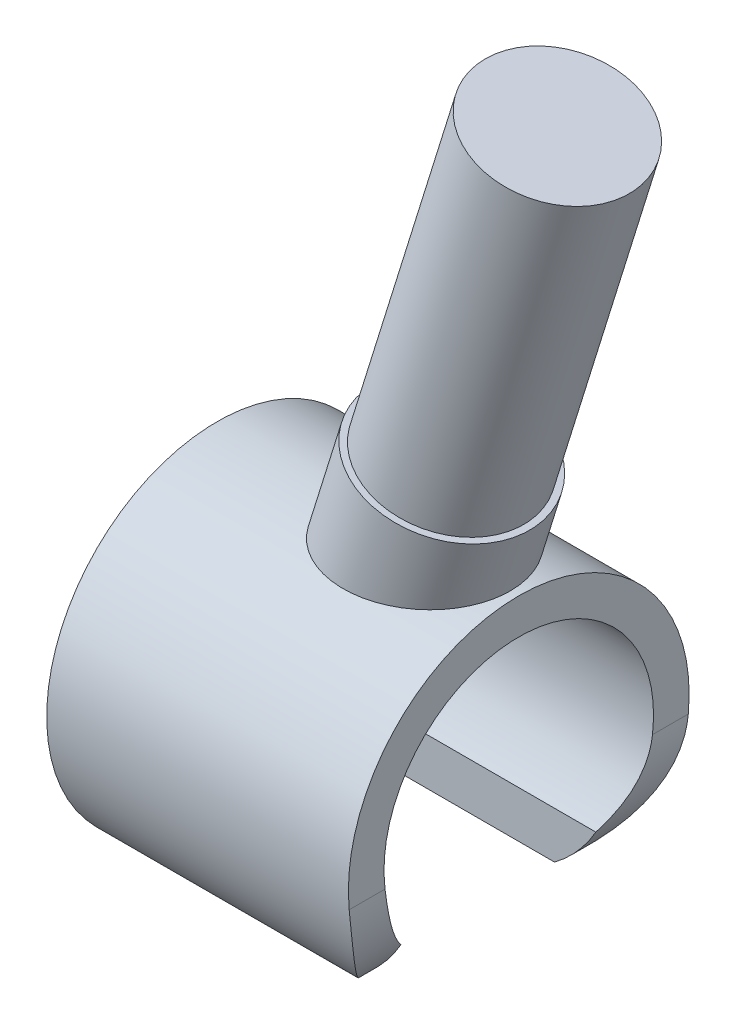
SolidWorks part; units mm, degrees
ref_plane "Ön Düzlem" through (0, 0, 0) normal (0, 0, 1) x (1, 0, 0)
ref_plane "Üst Düzlem" through (0, 0, 0) normal (0, 1, 0) x (1, 0, 0)
ref_plane "Sağ Düzlem" through (0, 0, 0) normal (1, 0, 0) x (0, 0, -1)
sketch "Çizim1" plane through (0, 0, 0) normal (0, 0, 1) x (1, 0, 0)
  line L0 (0, 0) -> (0, -4.88)
  line L1 (0, -4.88) -> (2.12, -4.88)
  line L2 (4.32, -2.68) -> (4.32, 0)
  line L3 (4.32, 0) -> (0, 0)
  line L4 (2.1331, -2.7014) -> (6.6255, 11.7309) construction
  line L5 (0, 0) -> (0, 12.8929) construction
  line L6 (1.7486, 0) -> (2.2429, 1.5877)
  line L7 (4.4771, 0.8923) -> (2.2429, 1.5877)
  line L8 (2.3288, 1.561) -> (2.7254, 2.8352)
  line L9 (2.7254, 2.8352) -> (3.8416, 6.421)
  line L10 (5.904, 5.779) -> (3.8416, 6.421)
  line L11 (4.7878, 2.1932) -> (5.904, 5.779)
  line L12 (4.3912, 0.919) -> (4.7878, 2.1932)
  line L13 (3.9829, -0.6955) -> (4.4771, 0.8923)
  arc A0 (4.32, -2.68) -> (2.12, -4.88) centre (2.12, -2.68) cw
  arc A1 (3.9829, -0.6955) -> (1.7486, 0) centre (3.4681, 1.5872) cw
  point P10 (3.36, 1.24)
  point P17 (4.8728, 6.1)
  point P19 (4.8728, 6.1)
  point P23 (3.36, 1.24)
  dimension "D6" = 2.2
  dimension "D11" = 2.34
  dimension "D1" = 4.32
  dimension "D2" = 17.29
  dimension "D3" = 1.17
  dimension "D4" = 1.24
  dimension "D5" = 3.36
  dimension "D7" = 4.88
  dimension "D8" = 0.09
  dimension "D9" = 1.3345
  dimension "D10" = 6.1
extrude "Yükseklik-Ekstrüzyon1" add sketch "Çizim1" along normal mid plane 4.88 contours L13 A1 L3 L0 L1 A0 L2 | A1 L13 L3 | L3 L13 L7 L6 | L7 L12 L11 L10 L9 L8 region at (1.9971, -2.4847, 0) region at (3.0575, 0.6363, 0) region at (3.133, -0.3188, 0) region at (4.1164, 3.67, 0)
sketch "Çizim2" plane through (0, 0, 0) normal (-1, 0, 0) x (0, 0, 1)
  line L0 (0, 0) -> (0, -4.88) construction
  line L1 (2.44, -4.88) -> (-2.44, -4.88) construction
  line L3 (-1.395, -3.7737) -> (-1.395, -4.4419)
  line L4 (1.395, -3.7737) -> (1.395, -4.4419)
  line L5 (-1.395, -4.4419) -> (-1.395, -4.88)
  line L6 (1.395, -4.4419) -> (1.395, -4.88)
  arc A1 (1.395, -3.7737) -> (-1.395, -3.7737) centre (0, -2.44) ccw
  arc A2 (1.395, -4.4419) -> (-1.395, -4.4419) centre (0, -2.44) ccw
  line M2 (-2.44, -4.88) -> (2.44, -4.88)
  dimension "D1" = 3.86
  dimension "D2" = 4.88
  dimension "D3" = 2.79
  dimension "D4" = 1.1063
extrude "Kes-Ekstrüzyon3" cut sketch "Çizim2" against normal through all contours A1 L0 L6 L4 M2 | L0 A1 L3 L5 M2 region at (0, -2.7343, 0.8154) region at (0, -2.7343, -0.8154)
sketch "Çizim4" plane through (2.1615, 6.944, 0) normal (0.2972, 0.9548, 0) x (0.9548, -0.2972, 0)
  line L0 (1.7596, 0) -> (3.9196, 0) construction
  line L1 (1.7596, -2.44) -> (1.7596, 2.44) construction
  line L2 (3.9196, -2.44) -> (3.9196, 2.44) construction
  line L3 (1.7596, 2.44) -> (3.9196, 2.44)
  line L4 (3.9196, 2.44) -> (3.9196, -2.44)
  line L5 (3.9196, -2.44) -> (1.7596, -2.44)
  line L6 (1.7596, -2.44) -> (1.7596, 2.44)
  circle A0 centre (2.8396, 0) radius 1.08
  line M2 (3.9196, 2.44) -> (1.7596, 2.44)
  line M3 (1.7596, 2.44) -> (1.7596, -2.44)
  line M4 (1.7596, -2.44) -> (3.9196, -2.44)
  line M5 (3.9196, -2.44) -> (3.9196, 2.44)
  dimension "D1" = 2.16
extrude "Kes-Ekstrüzyon4" cut sketch "Çizim4" against normal blind 5.09 contours A0 L4 M2 M3 | A0 L6 M4 M5 region at (4.8728, 6.1, -1.6259) region at (4.8728, 6.1, 1.6259)
sketch "Çizim5" plane through (0.6487, 2.084, 0) normal (0.2972, 0.9548, 0) x (0.9548, -0.2972, 0)
  line L0 (1.6696, 2.44) -> (4.0096, 2.44)
  line L1 (4.0096, 2.44) -> (4.0096, -2.44)
  line L2 (4.0096, -2.44) -> (1.6696, -2.44)
  line L3 (1.6696, -2.44) -> (1.6696, 2.44)
  circle A0 centre (2.8396, 0) radius 1.17
  line M2 (4.0096, 2.44) -> (1.6696, 2.44)
  line M3 (1.6696, 2.44) -> (1.6696, -2.44)
  line M4 (1.6696, -2.44) -> (4.0096, -2.44)
  line M5 (4.0096, -2.44) -> (4.0096, 2.44)
  dimension "D1" = 2.34
extrude "Kes-Ekstrüzyon5" cut sketch "Çizim5" against normal blind 0.9345 contours A0 L1 M2 M3 | A0 L3 M4 M5 region at (3.36, 1.24, -1.657) region at (3.36, 1.24, 1.657)
sketch "Çizim6" plane through (0, 0, 0) normal (-1, 0, 0) x (0, 0, 1)
  line L0 (-2.44, 0) -> (-2.44, -4.88)
  line L1 (-2.44, 0) -> (2.44, 0)
  line L2 (-2.44, -4.88) -> (-1.395, -4.88)
  line L3 (-1.395, -4.88) -> (-1.395, -4.4419)
  line L4 (-1.395, -3.7737) -> (-1.395, -4.88) construction
  line L5 (2.44, 0) -> (2.44, -4.88)
  line L6 (2.44, -4.88) -> (1.395, -4.88)
  line L7 (1.395, -4.88) -> (1.395, -4.4419)
  line L8 (1.395, -3.7737) -> (1.395, -4.88) construction
  line L9 (-2.44, 0) -> (0, 0)
  line L10 (2.44, 0) -> (0, 0)
  circle A0 centre (0, -2.44) radius 2.44
  line M1 (1.395, -3.7737) -> (1.395, -4.88)
  line M2 (1.395, -4.88) -> (2.44, -4.88)
  line M3 (2.44, -4.88) -> (2.44, 0)
  line M4 (2.44, 0) -> (-2.44, 0)
  line M5 (-2.44, 0) -> (-2.44, -4.88)
  line M6 (-2.44, -4.88) -> (-1.395, -4.88)
  line M7 (-1.395, -4.88) -> (-1.395, -3.7737)
  dimension "D1" = 4.88
  dimension "D2" = 4.88
extrude "Kes-Ekstrüzyon6" cut sketch "Çizim6" against normal through all contours A0 L1 M5 | A0 L5 M4 | A0 M1 M2 M3 | A0 L0 M6 M7 region at (0, -0.545, -1.895) region at (0, -4.2597, -2.0474) region at (0, -0.545, 1.895) region at (0, -4.2597, 2.0474)
sketch "Çizim7" plane through (0.6487, 2.084, 0) normal (0.2972, 0.9548, 0) x (0.9548, -0.2972, 0)
  circle A0 centre (2.8396, 0) radius 1.17
  dimension "D1" = 2.34
sketch "Çizim8" plane through (0.3709, 1.1917, 0) normal (0.2972, 0.9548, 0) x (0.9548, -0.2972, 0)
  line L0 (1.6696, 0) -> (1.6696, 2.44)
  line L1 (1.6696, 2.44) -> (4.0096, 2.44)
  line L2 (4.0096, 2.44) -> (4.0096, 0)
  line L3 (4.0096, 2.44) -> (4.0096, 0)
  circle A0 centre (2.8396, 0) radius 1.17
  arc M1 (1.6696, 0) -> (4.0096, 0) centre (2.8396, 0) cw
  line M2 (4.0096, 0) -> (4.0096, 2.44)
  line M3 (4.0096, 2.44) -> (1.6696, 2.44)
  line M4 (1.6696, 2.44) -> (1.6696, 0)
  dimension "D1" = 2.34
extrude "Kes-Ekstrüzyon8" cut sketch "Çizim8" against normal up to surface (2.5555 mm away) contours M4 M1 M2 M3 region at (3.0823, 0.3477, -1.657) up to face at (2.6338, -2.742, -0.0049)
sketch "Çizim9" plane through (0.3709, 1.1917, 0) normal (0.2972, 0.9548, 0) x (0.9548, -0.2972, 0)
  line L0 (1.6696, 0) -> (1.6696, -2.44)
  line L1 (1.6696, -2.44) -> (4.0096, -2.44)
  line L2 (4.0096, -2.44) -> (4.0096, 0)
  circle A0 centre (2.8396, 0) radius 1.17
  arc M1 (4.0096, 0) -> (1.6696, 0) centre (2.8396, 0) cw
  line M2 (1.6696, 0) -> (1.6696, -2.44)
  line M3 (1.6696, -2.44) -> (4.0096, -2.44)
  line M4 (4.0096, -2.44) -> (4.0096, 0)
  dimension "D1" = 2.34
extrude "Kes-Ekstrüzyon9" cut sketch "Çizim9" against normal up to surface (3.2839 mm away) contours M4 M1 M2 M3 region at (3.0823, 0.3477, 1.657) up to face at (2.6338, -2.742, -0.0049)
